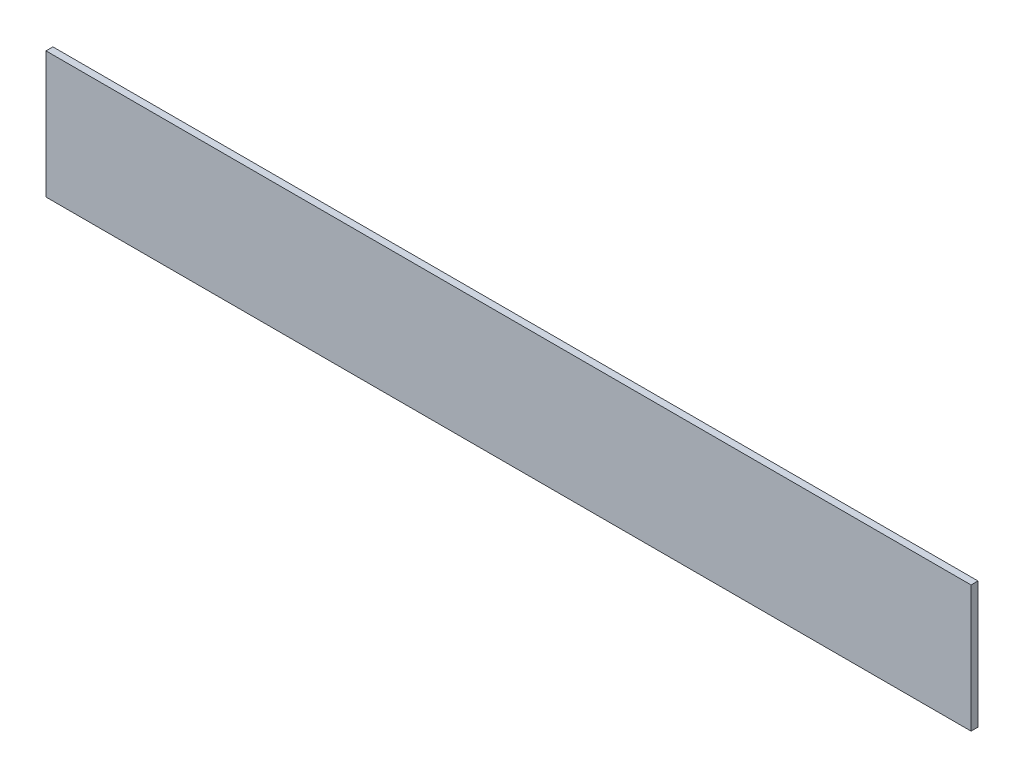
SolidWorks part; units mm, degrees
ref_plane "Front Plane" through (0, 0, 0) normal (0, 0, 1) x (1, 0, 0)
ref_plane "Top Plane" through (0, 0, 0) normal (0, 1, 0) x (1, 0, 0)
ref_plane "Right Plane" through (0, 0, 0) normal (1, 0, 0) x (0, 0, -1)
sketch "Sketch1" plane through (0, 0, 0) normal (0, 0, 1) x (1, 0, 0)
  line L0 (0, 0) -> (400, 0)
  line L1 (0, 0) -> (0, 54.75)
  line L2 (0, 54.75) -> (400, 54.75)
  line L3 (400, 54.75) -> (400, 0)
  dimension "D1" = 54.75
  dimension "D2" = 400
extrude "Boss-Extrude1" add sketch "Sketch1" along normal blind 3 contours L2 L3 L0 L1
